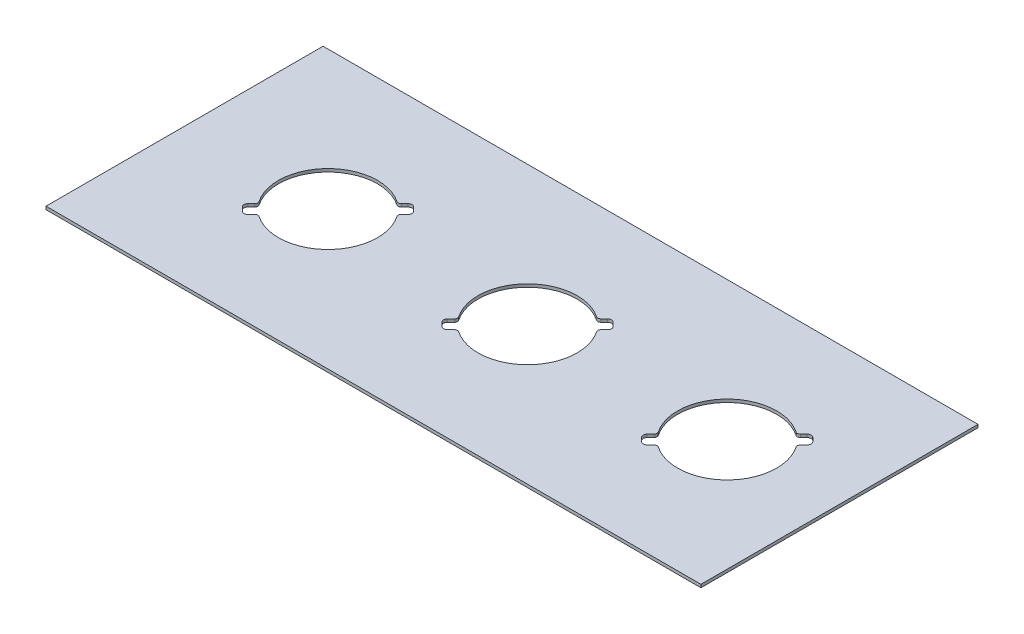
SolidWorks part; units mm, degrees
material "E-Glass Fiber"
ref_plane "Front" through (0, 0, 0) normal (0, 0, 1) x (1, 0, 0)
ref_plane "Top" through (0, 0, 0) normal (0, 1, 0) x (1, 0, 0)
ref_plane "Right" through (0, 0, 0) normal (1, 0, 0) x (0, 0, -1)
sketch "Sketch2" plane through (0, 0, 0) normal (0, 1, 0) x (1, 0, 0)
  line L0 (131.0347, 17.8011) -> (128.383, 15.1494) construction
  line L1 (-165.1, 69.85) -> (165.1, 69.85)
  line L2 (-165.1, 69.85) -> (-165.1, -69.85)
  line L3 (-165.1, -69.85) -> (165.1, -69.85)
  line L4 (165.1, 69.85) -> (165.1, -69.85)
  line L5 (-165.1, 69.85) -> (165.1, -69.85) construction
  line L6 (-165.1, -69.85) -> (165.1, 69.85) construction
  line L7 (85.9573, -17.8011) -> (88.609, -15.1494) construction
  line L8 (87.8665, -22.5387) -> (85.9573, -20.6295) construction
  line L9 (93.3466, -19.887) -> (90.6949, -22.5387) construction
  line L10 (85.9573, -17.8011) -> (87.654, -16.1044)
  line L11 (87.8665, -22.5387) -> (85.9573, -20.6295)
  line L12 (92.3916, -20.842) -> (90.6949, -22.5387)
  line L13 (129.1255, 22.5387) -> (131.0347, 20.6295) construction
  line L14 (123.6454, 19.887) -> (126.2971, 22.5387) construction
  line L15 (124.6004, 20.842) -> (126.2971, 22.5387)
  line L16 (129.1255, 22.5387) -> (131.0347, 20.6295)
  line L17 (131.0347, 17.8011) -> (129.338, 16.1044)
  line L18 (-14.6777, -17.8011) -> (-12.026, -15.1494) construction
  line L19 (-12.7685, -22.5387) -> (-14.6777, -20.6295) construction
  line L20 (-7.2884, -19.887) -> (-9.9401, -22.5387) construction
  line L21 (-14.6777, -17.8011) -> (-12.981, -16.1044)
  line L22 (-12.7685, -22.5387) -> (-14.6777, -20.6295)
  line L23 (-8.2434, -20.842) -> (-9.9401, -22.5387)
  line L24 (30.3997, 17.8011) -> (27.748, 15.1494) construction
  line L25 (28.4905, 22.5387) -> (30.3997, 20.6295) construction
  line L26 (23.0104, 19.887) -> (25.6621, 22.5387) construction
  line L27 (30.3997, 17.8011) -> (28.703, 16.1044)
  line L28 (28.4905, 22.5387) -> (30.3997, 20.6295)
  line L29 (23.9654, 20.842) -> (25.6621, 22.5387)
  line L30 (-115.3127, -17.8011) -> (-112.661, -15.1494) construction
  line L31 (-113.4035, -22.5387) -> (-115.3127, -20.6295) construction
  line L32 (-107.9234, -19.887) -> (-110.5751, -22.5387) construction
  line L33 (-115.3127, -17.8011) -> (-113.616, -16.1044)
  line L34 (-113.4035, -22.5387) -> (-115.3127, -20.6295)
  line L35 (-108.8784, -20.842) -> (-110.5751, -22.5387)
  line L36 (-77.6246, 19.887) -> (-74.9729, 22.5387) construction
  line L37 (-72.1445, 22.5387) -> (-70.2353, 20.6295) construction
  line L38 (-70.2353, 17.8011) -> (-72.887, 15.1494) construction
  line L39 (-76.6696, 20.842) -> (-74.9729, 22.5387)
  line L40 (-72.1445, 22.5387) -> (-70.2353, 20.6295)
  line L41 (-70.2353, 17.8011) -> (-71.932, 16.1044)
  arc A0 (-6.2263, -20.653) -> (28.514, 14.0873) centre (7.861, 0) ccw
  arc A1 (94.4087, -20.653) -> (129.149, 14.0873) centre (108.496, 0) ccw
  arc A2 (-106.8613, -20.653) -> (-72.121, 14.0873) centre (-92.774, 0) ccw
  arc A3 (93.3466, -19.887) -> (123.6454, -19.887) centre (108.496, 0) ccw construction
  arc A4 (-7.2884, -19.887) -> (23.0104, -19.887) centre (7.861, 0) ccw construction
  arc A5 (-112.661, 15.1494) -> (-112.661, -15.1494) centre (-92.774, 0) ccw construction
  arc A6 (85.9573, -17.8011) -> (85.9573, -20.6295) centre (87.3715, -19.2153) ccw construction
  arc A7 (87.8665, -22.5387) -> (90.6949, -22.5387) centre (89.2807, -21.1245) ccw construction
  arc A8 (85.9573, -17.8011) -> (85.9573, -20.6295) centre (87.3715, -19.2153) ccw
  arc A9 (87.8665, -22.5387) -> (90.6949, -22.5387) centre (89.2807, -21.1245) ccw
  arc A10 (131.0347, 17.8011) -> (131.0347, 20.6295) centre (129.6205, 19.2153) ccw construction
  arc A11 (129.1255, 22.5387) -> (126.2971, 22.5387) centre (127.7113, 21.1245) ccw construction
  arc A12 (129.1255, 22.5387) -> (126.2971, 22.5387) centre (127.7113, 21.1245) ccw
  arc A13 (131.0347, 17.8011) -> (131.0347, 20.6295) centre (129.6205, 19.2153) ccw
  arc A14 (122.5833, 20.653) -> (87.843, -14.0873) centre (108.496, 0) ccw
  arc A15 (-14.6777, -17.8011) -> (-14.6777, -20.6295) centre (-13.2635, -19.2153) ccw construction
  arc A16 (-12.7685, -22.5387) -> (-9.9401, -22.5387) centre (-11.3543, -21.1245) ccw construction
  arc A17 (-14.6777, -17.8011) -> (-14.6777, -20.6295) centre (-13.2635, -19.2153) ccw
  arc A18 (-12.7685, -22.5387) -> (-9.9401, -22.5387) centre (-11.3543, -21.1245) ccw
  arc A19 (30.3997, 17.8011) -> (30.3997, 20.6295) centre (28.9855, 19.2153) ccw construction
  arc A20 (28.4905, 22.5387) -> (25.6621, 22.5387) centre (27.0763, 21.1245) ccw construction
  arc A21 (30.3997, 17.8011) -> (30.3997, 20.6295) centre (28.9855, 19.2153) ccw
  arc A22 (28.4905, 22.5387) -> (25.6621, 22.5387) centre (27.0763, 21.1245) ccw
  arc A23 (-115.3127, -17.8011) -> (-115.3127, -20.6295) centre (-113.8985, -19.2153) ccw construction
  arc A24 (-113.4035, -22.5387) -> (-110.5751, -22.5387) centre (-111.9893, -21.1245) ccw construction
  arc A25 (-115.3127, -17.8011) -> (-115.3127, -20.6295) centre (-113.8985, -19.2153) ccw
  arc A26 (-113.4035, -22.5387) -> (-110.5751, -22.5387) centre (-111.9893, -21.1245) ccw
  arc A27 (-72.1445, 22.5387) -> (-74.9729, 22.5387) centre (-73.5587, 21.1245) ccw construction
  arc A28 (-70.2353, 17.8011) -> (-70.2353, 20.6295) centre (-71.6495, 19.2153) ccw construction
  arc A29 (-72.1445, 22.5387) -> (-74.9729, 22.5387) centre (-73.5587, 21.1245) ccw
  arc A30 (-70.2353, 17.8011) -> (-70.2353, 20.6295) centre (-71.6495, 19.2153) ccw
  arc A31 (-78.6867, 20.653) -> (-113.427, -14.0873) centre (-92.774, 0) ccw
  arc A32 (21.9483, 20.653) -> (-12.792, -14.0873) centre (7.861, 0) ccw
  arc A33 (-76.6696, 20.842) -> (-78.6867, 20.653) centre (-77.7922, 21.9645) cw
  arc A34 (-71.932, 16.1044) -> (-72.121, 14.0873) centre (-70.8095, 14.9818) ccw
  arc A35 (-113.616, -16.1044) -> (-113.427, -14.0873) centre (-114.7385, -14.9818) ccw
  arc A36 (-108.8784, -20.842) -> (-106.8613, -20.653) centre (-107.7558, -21.9645) cw
  arc A37 (-12.981, -16.1044) -> (-12.792, -14.0873) centre (-14.1035, -14.9818) ccw
  arc A38 (-8.2434, -20.842) -> (-6.2263, -20.653) centre (-7.1208, -21.9645) cw
  arc A39 (23.9654, 20.842) -> (21.9483, 20.653) centre (22.8428, 21.9645) cw
  arc A40 (28.703, 16.1044) -> (28.514, 14.0873) centre (29.8255, 14.9818) ccw
  arc A41 (124.6004, 20.842) -> (122.5833, 20.653) centre (123.4778, 21.9645) cw
  arc A42 (129.338, 16.1044) -> (129.149, 14.0873) centre (130.4605, 14.9818) ccw
  arc A43 (92.3916, -20.842) -> (94.4087, -20.653) centre (93.5142, -21.9645) cw
  arc A44 (87.654, -16.1044) -> (87.843, -14.0873) centre (86.5315, -14.9818) ccw
  point P0 (0, 0)
  dimension "D3" = 1.5875
  dimension "D1" = 330.2
  dimension "D2" = 139.7
extrude "Boss-Extrude1" add sketch "Sketch2" along normal blind 1.524
sketch "Sketch3" plane through (0, 1.524, 0) normal (0, 1, 0) x (1, 0, 0)
  line L42 (-165.1, -69.85) -> (-139.7, -69.85) construction
  line L44 (-165.1, 69.85) -> (-139.7, 69.85) construction
  line L45 (-165.1, 49.8475) -> (-165.1, 69.85) construction
  line L46 (-139.7, -88.9) -> (-139.7, 88.9) construction
  line L47 (-139.7, -69.85) -> (-139.7, 69.85)
  line L48 (-139.7, 49.8475) -> (-165.1, 49.8475)
  line L49 (-165.1, 69.85) -> (-165.1, -69.85) construction
  line L50 (-139.7, -49.8475) -> (-165.1, -49.8475)
  line L51 (-165.1, -49.8475) -> (-165.1, -69.85) construction
  line L54 (82.226, 26.27) -> (134.766, 26.27) construction
  line L56 (108.496, 26.27) -> (134.766, 26.27)
  line L58 (134.766, 26.27) -> (134.766, -26.27) construction
  line L60 (134.766, 26.27) -> (134.766, 0)
  line L62 (134.766, 0) -> (133.496, 0)
  line L64 (123.6454, 19.887) -> (126.2971, 22.5387) construction
  line L65 (131.0347, 20.6295) -> (129.1255, 22.5387) construction
  line L66 (131.0347, 20.6295) -> (129.1255, 22.5387)
  line L68 (123.6454, 19.887) -> (126.2971, 22.5387)
  line L70 (131.0347, 17.8011) -> (128.383, 15.1494) construction
  line L71 (131.0347, 17.8011) -> (128.383, 15.1494)
  line L72 (108.496, 25) -> (108.496, 26.27)
  line L73 (108.496, 0) -> (108.496, 25) construction
  line L74 (82.226, -26.27) -> (82.226, 26.27) construction
  line L75 (82.226, -26.27) -> (82.226, 0)
  line L76 (134.766, -26.27) -> (82.226, -26.27) construction
  line L77 (108.496, -26.27) -> (82.226, -26.27)
  line L78 (108.496, 0) -> (108.496, -25) construction
  line L79 (108.496, -25) -> (108.496, -26.27)
  line L80 (83.496, 0) -> (82.226, 0)
  line L81 (85.9573, -17.8011) -> (88.609, -15.1494) construction
  line L82 (85.9573, -17.8011) -> (88.609, -15.1494)
  line L83 (85.9573, -20.6295) -> (87.8665, -22.5387) construction
  line L84 (85.9573, -20.6295) -> (87.8665, -22.5387)
  line L85 (93.3466, -19.887) -> (90.6949, -22.5387) construction
  line L86 (93.3466, -19.887) -> (90.6949, -22.5387)
  line L87 (108.496, 0) -> (83.496, 0) construction
  line L88 (-18.409, 26.27) -> (34.131, 26.27) construction
  line L89 (7.861, 26.27) -> (34.131, 26.27)
  line L90 (34.131, 26.27) -> (34.131, -26.27) construction
  line L91 (34.131, 26.27) -> (34.131, 0)
  line L92 (-18.409, -26.27) -> (-18.409, 26.27) construction
  line L93 (-18.409, -26.27) -> (-18.409, 0)
  line L94 (34.131, -26.27) -> (-18.409, -26.27) construction
  line L95 (7.861, -26.27) -> (-18.409, -26.27)
  line L96 (-66.504, -26.27) -> (-119.044, -26.27) construction
  line L97 (-92.774, -26.27) -> (-119.044, -26.27)
  line L98 (-66.504, 26.27) -> (-66.504, -26.27) construction
  line L99 (-66.504, 26.27) -> (-66.504, 0)
  line L100 (-119.044, 26.27) -> (-66.504, 26.27) construction
  line L101 (-92.774, 26.27) -> (-66.504, 26.27)
  line L102 (-119.044, -26.27) -> (-119.044, 26.27) construction
  line L103 (-119.044, -26.27) -> (-119.044, 0)
  line L104 (30.3997, 17.8011) -> (27.748, 15.1494) construction
  line L105 (30.3997, 20.6295) -> (28.4905, 22.5387) construction
  line L106 (23.0104, 19.887) -> (25.6621, 22.5387) construction
  line L107 (30.3997, 17.8011) -> (27.748, 15.1494)
  line L108 (30.3997, 20.6295) -> (28.4905, 22.5387)
  line L109 (23.0104, 19.887) -> (25.6621, 22.5387)
  line L110 (-7.2884, -19.887) -> (-9.9401, -22.5387) construction
  line L112 (-14.6777, -20.6295) -> (-12.7685, -22.5387) construction
  line L113 (-14.6777, -17.8011) -> (-12.026, -15.1494) construction
  line L114 (-14.6777, -17.8011) -> (-12.026, -15.1494)
  line L115 (-14.6777, -20.6295) -> (-12.7685, -22.5387)
  line L116 (-7.2884, -19.887) -> (-9.9401, -22.5387)
  line L121 (-70.2353, 20.6295) -> (-72.1445, 22.5387) construction
  line L122 (-77.6246, 19.887) -> (-74.9729, 22.5387) construction
  line L123 (-70.2353, 17.8011) -> (-72.887, 15.1494) construction
  line L124 (-70.2353, 20.6295) -> (-72.1445, 22.5387)
  line L125 (-115.3127, -20.6295) -> (-113.4035, -22.5387) construction
  line L126 (-107.9234, -19.887) -> (-110.5751, -22.5387) construction
  line L127 (-115.3127, -17.8011) -> (-112.661, -15.1494) construction
  line L128 (-115.3127, -20.6295) -> (-113.4035, -22.5387)
  line L129 (-107.9234, -19.887) -> (-110.5751, -22.5387)
  line L130 (-115.3127, -17.8011) -> (-112.661, -15.1494)
  line L131 (7.861, 0) -> (7.861, 25) construction
  line L132 (7.861, 0) -> (32.861, 0) construction
  line L133 (7.861, 0) -> (7.861, -25) construction
  line L134 (7.861, 0) -> (-17.139, 0) construction
  line L135 (-92.774, 0) -> (-92.774, 25) construction
  line L136 (-92.774, 0) -> (-67.774, 0) construction
  line L137 (-92.774, 0) -> (-92.774, -25) construction
  line L138 (-92.774, 0) -> (-117.774, 0) construction
  line L139 (7.861, 25) -> (7.861, 26.27)
  line L140 (32.861, 0) -> (34.131, 0)
  line L141 (7.861, -25) -> (7.861, -26.27)
  line L142 (-17.139, 0) -> (-18.409, 0)
  line L143 (-67.774, 0) -> (-66.504, 0)
  line L144 (-92.774, 25) -> (-92.774, 26.27)
  line L145 (-117.774, 0) -> (-119.044, 0)
  line L146 (-92.774, -25) -> (-92.774, -26.27)
  line L147 (-77.6246, 19.887) -> (-74.9729, 22.5387)
  line L148 (-70.2353, 17.8011) -> (-72.887, 15.1494)
  line L149 (133.496, 0) -> (108.496, 0) construction
  arc A25 (123.6454, 19.887) -> (93.3466, 19.887) centre (108.496, 0) ccw construction
  arc A27 (123.6454, 19.887) -> (108.496, 25) centre (108.496, 0) ccw
  arc A28 (128.383, -15.1494) -> (128.383, 15.1494) centre (108.496, 0) ccw construction
  arc A29 (133.496, 0) -> (128.383, 15.1494) centre (108.496, 0) ccw
  arc A30 (129.1255, 22.5387) -> (126.2971, 22.5387) centre (127.7113, 21.1245) ccw construction
  arc A31 (129.1255, 22.5387) -> (126.2971, 22.5387) centre (127.7113, 21.1245) ccw
  arc A32 (131.0347, 17.8011) -> (131.0347, 20.6295) centre (129.6205, 19.2153) ccw construction
  arc A33 (131.0347, 17.8011) -> (131.0347, 20.6295) centre (129.6205, 19.2153) ccw
  arc A34 (122.5833, 20.653) -> (87.843, -14.0873) centre (108.496, 0) ccw construction
  arc A35 (88.609, 15.1494) -> (88.609, -15.1494) centre (108.496, 0) ccw construction
  arc A36 (83.496, 0) -> (88.609, -15.1494) centre (108.496, 0) ccw
  arc A37 (93.3466, -19.887) -> (123.6454, -19.887) centre (108.496, 0) ccw construction
  arc A38 (93.3466, -19.887) -> (108.496, -25) centre (108.496, 0) ccw
  arc A39 (85.9573, -17.8011) -> (85.9573, -20.6295) centre (87.3715, -19.2153) ccw construction
  arc A40 (85.9573, -17.8011) -> (85.9573, -20.6295) centre (87.3715, -19.2153) ccw
  arc A41 (87.8665, -22.5387) -> (90.6949, -22.5387) centre (89.2807, -21.1245) ccw construction
  arc A42 (87.8665, -22.5387) -> (90.6949, -22.5387) centre (89.2807, -21.1245) ccw
  arc A44 (27.748, -15.1494) -> (27.748, 15.1494) centre (7.861, 0) ccw construction
  arc A46 (32.861, 0) -> (27.748, 15.1494) centre (7.861, 0) ccw
  arc A48 (-72.887, -15.1494) -> (-72.887, 15.1494) centre (-92.774, 0) ccw construction
  arc A50 (-67.774, 0) -> (-72.887, 15.1494) centre (-92.774, 0) ccw
  arc A51 (30.3997, 17.8011) -> (30.3997, 20.6295) centre (28.9855, 19.2153) ccw construction
  arc A52 (28.4905, 22.5387) -> (25.6621, 22.5387) centre (27.0763, 21.1245) ccw construction
  arc A53 (30.3997, 17.8011) -> (30.3997, 20.6295) centre (28.9855, 19.2153) ccw
  arc A54 (28.4905, 22.5387) -> (25.6621, 22.5387) centre (27.0763, 21.1245) ccw
  arc A55 (23.0104, 19.887) -> (-7.2884, 19.887) centre (7.861, 0) ccw construction
  arc A56 (23.0104, 19.887) -> (7.861, 25) centre (7.861, 0) ccw
  arc A57 (-7.2884, -19.887) -> (23.0104, -19.887) centre (7.861, 0) ccw construction
  arc A58 (-7.2884, -19.887) -> (7.861, -25) centre (7.861, 0) ccw
  arc A59 (-12.026, 15.1494) -> (-12.026, -15.1494) centre (7.861, 0) ccw construction
  arc A60 (-17.139, 0) -> (-12.026, -15.1494) centre (7.861, 0) ccw
  arc A61 (-12.7685, -22.5387) -> (-9.9401, -22.5387) centre (-11.3543, -21.1245) ccw construction
  arc A62 (-14.6777, -17.8011) -> (-14.6777, -20.6295) centre (-13.2635, -19.2153) ccw construction
  arc A63 (-14.6777, -17.8011) -> (-14.6777, -20.6295) centre (-13.2635, -19.2153) ccw
  arc A64 (-12.7685, -22.5387) -> (-9.9401, -22.5387) centre (-11.3543, -21.1245) ccw
  arc A65 (-77.6246, 19.887) -> (-107.9234, 19.887) centre (-92.774, 0) ccw construction
  arc A66 (-77.6246, 19.887) -> (-92.774, 25) centre (-92.774, 0) ccw
  arc A67 (-112.661, 15.1494) -> (-112.661, -15.1494) centre (-92.774, 0) ccw construction
  arc A68 (-117.774, 0) -> (-112.661, -15.1494) centre (-92.774, 0) ccw
  arc A69 (-107.9234, -19.887) -> (-77.6246, -19.887) centre (-92.774, 0) ccw construction
  arc A70 (-107.9234, -19.887) -> (-92.774, -25) centre (-92.774, 0) ccw
  arc A73 (-70.2353, 17.8011) -> (-70.2353, 20.6295) centre (-71.6495, 19.2153) ccw construction
  arc A74 (-72.1445, 22.5387) -> (-74.9729, 22.5387) centre (-73.5587, 21.1245) ccw construction
  arc A75 (-115.3127, -17.8011) -> (-115.3127, -20.6295) centre (-113.8985, -19.2153) ccw construction
  arc A76 (-113.4035, -22.5387) -> (-110.5751, -22.5387) centre (-111.9893, -21.1245) ccw construction
  arc A77 (-115.3127, -17.8011) -> (-115.3127, -20.6295) centre (-113.8985, -19.2153) ccw
  arc A78 (-113.4035, -22.5387) -> (-110.5751, -22.5387) centre (-111.9893, -21.1245) ccw
  arc A79 (-70.2353, 17.8011) -> (-70.2353, 20.6295) centre (-71.6495, 19.2153) ccw
  arc A80 (-72.1445, 22.5387) -> (-74.9729, 22.5387) centre (-73.5587, 21.1245) ccw
  dimension "D1" = 99.695
